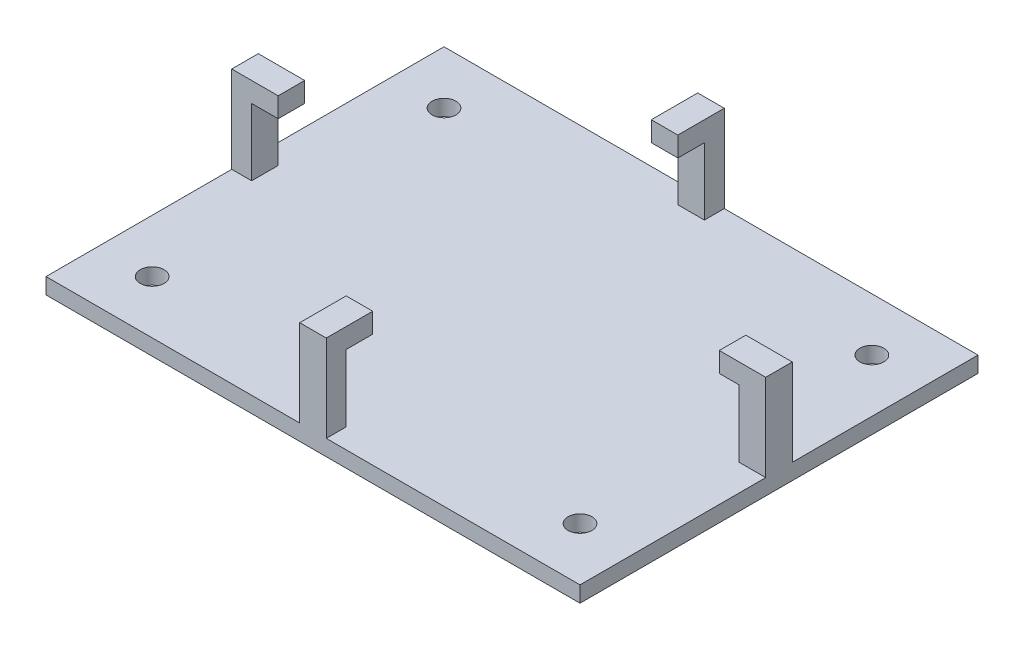
SolidWorks part; units mm, degrees
ref_plane "Front Plane" through (0, 0, 0) normal (0, 0, 1) x (1, 0, 0)
ref_plane "Top Plane" through (0, 0, 0) normal (0, 1, 0) x (1, 0, 0)
ref_plane "Right Plane" through (0, 0, 0) normal (1, 0, 0) x (0, 0, -1)
sketch "Sketch2" plane through (0, 0, 0) normal (0, 1, 0) x (1, 0, 0)
  line L0 (37.25, 27) -> (-37.25, 27) construction
  line L5 (-36.25, 26) -> (36.25, -26) construction
  line L6 (36.25, -26) -> (-36.25, -26)
  line L7 (36.25, -26) -> (36.25, 26)
  line L8 (36.25, 26) -> (-36.25, 26)
  line L9 (-36.25, -26) -> (-36.25, 26)
  line L10 (36.25, 26) -> (-36.25, -26) construction
  line L11 (-34.85, 24.6) -> (-34.85, 26) construction
  line L12 (-34.85, 26) -> (-34.85, 24.6)
  line L13 (-36.25, 24.6) -> (-34.85, 24.6) construction
  line L14 (0, 26) -> (0, -26) construction
  line L15 (40.25, 2) -> (36.25, 2)
  line L16 (-37.25, -27) -> (-37.25, 27) construction
  line L17 (37.25, -27) -> (-37.25, -27) construction
  line L18 (37.25, -27) -> (37.25, 27) construction
  line L19 (40.25, 30) -> (-40.25, 30)
  line L20 (-40.25, -30) -> (-40.25, 30)
  line L21 (40.25, -30) -> (-40.25, -30)
  line L22 (40.25, -30) -> (40.25, 30)
  line L23 (0, -26) -> (0, -30) construction
  line L24 (-40.25, -2) -> (-36.25, -2)
  line L25 (-40.25, -2) -> (-40.25, 2)
  line L26 (-40.25, 2) -> (-36.25, 2)
  line L27 (-36.25, -2) -> (-36.25, 2)
  line L28 (-40.25, -2) -> (-36.25, 2) construction
  line L29 (-40.25, 2) -> (-36.25, -2) construction
  line L30 (-2, -30) -> (2, -30)
  line L31 (-2, -30) -> (-2, -26)
  line L32 (-2, -26) -> (2, -26)
  line L33 (2, -30) -> (2, -26)
  line L34 (-2, -30) -> (2, -26) construction
  line L35 (-2, -26) -> (2, -30) construction
  line L37 (0, -55) -> (0, 55) construction
  line L40 (40.25, -2) -> (40.25, 2)
  line L41 (40.25, -2) -> (36.25, -2)
  line L42 (-2, 26) -> (2, 30) construction
  line L43 (-2, 30) -> (2, 26) construction
  line L44 (-55, 0) -> (55, 0) construction
  line L45 (2, 30) -> (2, 26)
  line L46 (-2, 26) -> (2, 26)
  line L47 (-2, 30) -> (-2, 26)
  line L48 (-2, 30) -> (2, 30)
  line L49 (-37.25, 2) -> (-37.25, -2)
  line L50 (-2, -27) -> (2, -27)
  line L52 (-2, 27) -> (2, 27)
  circle A6 centre (-103.863, -60.972) radius 1
  circle A8 centre (-32.25, -22) radius 1.8
  circle A9 centre (32.25, -22) radius 1.8
  circle A10 centre (32.25, 22) radius 1.8
  circle A11 centre (-32.25, 22) radius 1.8
  point P7 (0, 0)
  point P12 (0, 0)
  point P18 (0, 28)
  point P20 (36.1499, -2)
  point P27 (-38.25, 0)
  point P32 (0, -28)
  point P37 (0, -28)
  point P58 (0, 0)
  dimension "D17" = 3.6
  dimension "D2" = 1.4
  dimension "D3" = 72.5
  dimension "D4" = 52
  dimension "D5" = 4
  dimension "D6" = 4
  dimension "D7" = 4
  dimension "D8" = 4
  dimension "D9" = 4
  dimension "D10" = 1
  dimension "D11" = 1
  dimension "D12" = 1
  dimension "D13" = 1
  dimension "D15" = 4
  dimension "D16" = 4
  dimension "D18" = 4
  dimension "D19" = 4
  dimension "D20" = 2
extrude "Boss-Extrude1" add sketch "Sketch2" along normal blind 2.4 contours L8 L9 L6 L7 | L47 L19 L20 L26 L9 L8 | L21 L31 L6 L9 L24 L20 | L49 L26 L20 L24 | L26 L49 L24 L9 | L50 L31 L21 L33 | L31 L50 L33 L6 | L22 L41 L7 L6 L33 L21 | L41 L22 L15 L7 | L19 L45 L8 L7 L15 L22 | L47 L52 L45 L19 | L52 L47 L8 L45 region at (36.724, 0, 14) region at (0, 0, 0) region at (0, 0, 26.5) region at (38.25, 0, 0) region at (-2.474, 0, 26.5) region at (0, 0, 28.5) region at (36.724, 0, -14) region at (-36.75, 0, 0) region at (0, 0, -26.5) region at (-36.75, 0, -2.474) region at (-38.75, 0, 0) region at (0, 0, -28.5)
extrude "Boss-Extrude2" add sketch "Sketch2<3>" along normal blind 12.5 contours L50 L31 L21 L33 | L41 L22 L15 L7 | L47 L52 L45 L19 | L49 L26 L20 L24 region at (38.25, 0, 0) region at (0, 0, 28.5) region at (-38.75, 0, 0) region at (0, 0, -28.5)
sketch "Sketch2<3>" plane through (0, 0, 0) normal (0, 1, 0) x (1, 0, 0) same geometry as "Sketch2"
sketch "Sketch3" plane through (0, 12.5, 0) normal (0, 1, 0) x (1, 0, 0)
  line L0 (2, 30) -> (2, 27) construction
  line L1 (-2, 30) -> (2, 30)
  line L2 (-2, 30) -> (-2, 23)
  line L3 (-2, 23) -> (2, 23)
  line L4 (2, 30) -> (2, 23)
  line L5 (-40.25, -2) -> (-37.25, -2) construction
  line L6 (-40.25, 2) -> (-33.25, 2)
  line L7 (-40.25, 2) -> (-40.25, -2)
  line L8 (-40.25, -2) -> (-33.25, -2)
  line L9 (-33.25, 2) -> (-33.25, -2)
  line L10 (2, -30) -> (2, -27) construction
  line L11 (-2, -30) -> (2, -30)
  line L12 (-2, -30) -> (-2, -23)
  line L13 (-2, -23) -> (2, -23)
  line L14 (2, -30) -> (2, -23)
  line L15 (40.25, -2) -> (36.25, -2) construction
  line L16 (40.25, 2) -> (33.25, 2)
  line L17 (40.25, 2) -> (40.25, -2)
  line L18 (40.25, -2) -> (33.25, -2)
  line L19 (33.25, 2) -> (33.25, -2)
  dimension "D1" = 7
  dimension "D2" = 7
  dimension "D3" = 7
  dimension "D4" = 7
extrude "Boss-Extrude3" add sketch "Sketch3" along normal blind 3
